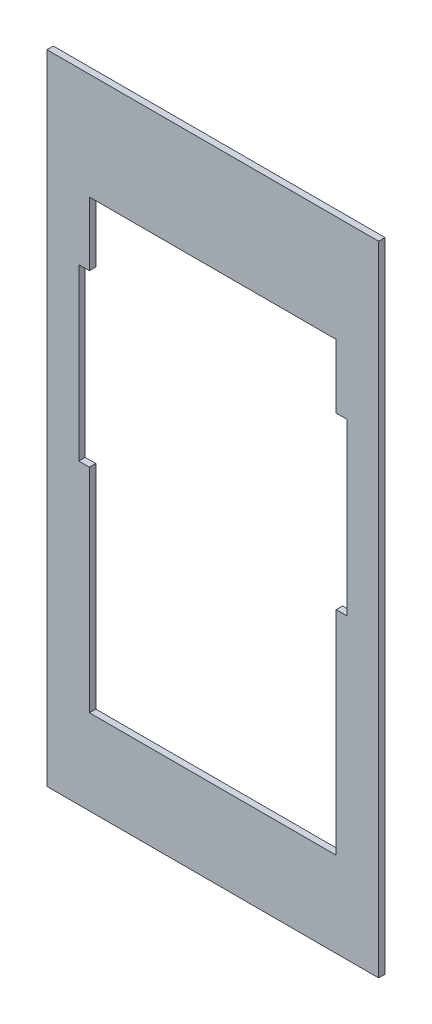
SolidWorks part; units mm, degrees
ref_plane "Front Plane" through (0, 0, 0) normal (0, 0, 1) x (1, 0, 0)
ref_plane "Top Plane" through (0, 0, 0) normal (0, 1, 0) x (1, 0, 0)
ref_plane "Right Plane" through (0, 0, 0) normal (1, 0, 0) x (0, 0, -1)
sketch "Sketch1" plane through (0, 0, 0) normal (0, 0, 1) x (1, 0, 0)
  line L1 (39, 75) -> (-39, 75)
  line L2 (39, 75) -> (39, -75)
  line L3 (39, -75) -> (-39, -75)
  line L4 (-39, 75) -> (-39, -75)
  line L5 (39, 75) -> (-39, -75) construction
  line L6 (39, -75) -> (-39, 75) construction
  line L20 (0, 0) -> (0, 75) construction
  line L21 (0, 0) -> (0, -75) construction
  line L23 (29, 50) -> (-29, 50)
  line L26 (-29, 50) -> (-29, 35)
  line L27 (-29, -55) -> (29, -55)
  line L33 (-29, 35) -> (-31.5, 35)
  line L35 (-29, -5) -> (-31.5, -5)
  line L36 (-31.5, 35) -> (-31.5, -5)
  line L37 (-29, -5) -> (-29, -55)
  line L38 (29, -5) -> (29, -55)
  line L39 (29, -5) -> (31.5, -5)
  line L40 (31.5, 35) -> (31.5, -5)
  line L41 (29, 35) -> (31.5, 35)
  line L42 (29, 50) -> (29, 35)
  point P0 (0, 0)
  dimension "D2" = 2.5
  dimension "D3" = 10
  dimension "D4" = 50
  dimension "D5" = 150
  dimension "D6" = 25
  dimension "D7" = 39
  dimension "D8" = 40
  dimension "D11" = 15
extrude "Boss-Extrude1" add sketch "Sketch1" along normal blind 1.5
